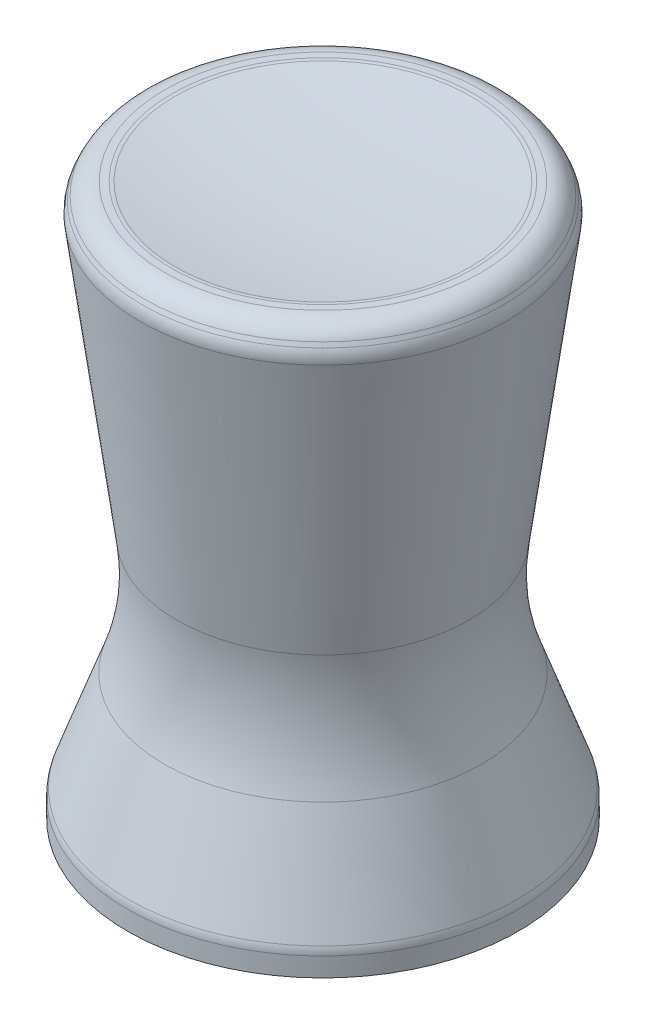
SolidWorks part; units mm, degrees
ref_plane "Front Plane" through (0, 0, 0) normal (0, 0, 1) x (1, 0, 0)
ref_plane "Top Plane" through (0, 0, 0) normal (0, 1, 0) x (1, 0, 0)
ref_plane "Right Plane" through (0, 0, 0) normal (1, 0, 0) x (0, 0, -1)
sketch "Sketch1" plane through (0, 0, 0) normal (0, 0, 1) x (1, 0, 0)
  line L0 (0, 0) -> (8.5, 0)
  line L1 (8.5, 0) -> (8.5, 1)
  line L2 (8.5, 1) -> (6, 8)
  line L3 (6, 8) -> (8, 23)
  line L4 (8, 23) -> (7.5, 24)
  line L5 (7.5, 24) -> (6.5, 24)
  line L6 (6.5, 24) -> (3.2692, 23.5) construction
  line L7 (0, 23.5) -> (0, 0) construction
  line L8 (0, 0) -> (0, 23.5)
  line L9 (3.2692, 23.5) -> (0, 23.5) construction
  spline S0 degree 2 poles (6.5, 24) (3.2692, 23.5) (0, 23.5) knots 0 0 0 1 1 1
  dimension "D1" = 24
  dimension "D2" = 8
  dimension "D3" = 1
  dimension "D4" = 8
  dimension "D5" = 1
  dimension "D6" = 0.5
  dimension "D7" = 0.5
  dimension "D8" = 1
  dimension "D9" = 8.5
  dimension "D10" = 6
revolve "Revolve1" add sketch "Sketch1" angle 360 about L7
fillet "Fillet1" radius 11 1 edges at (-6, 8, 0)
fillet "Fillet2" radius 1 4 edges at (-6.5, 24, 0) (-7.5, 24, 0) (-8, 23, 0) (-8.5, 1, 0)
sketch "Sketch3" plane through (0, 0, 0) normal (0, 0, 1) x (1, 0, 0)
  line L0 (0, 0) -> (3.875, 0)
  line L1 (-8.5, 0) -> (8.5, 0) construction
  line L2 (3.875, 0) -> (3.875, 6.5)
  line L3 (3.875, 6.5) -> (3.05, 7.325)
  line L4 (3.05, 7.325) -> (3.05, 17.75)
  line L5 (3.05, 17.75) -> (0, 17.75)
  line L6 (0, 17.75) -> (0, 0)
  dimension "D1" = 17.75
  dimension "D2" = 3.875
  dimension "D3" = 45
  dimension "D4" = 3.05
  dimension "D5" = 6.5
revolve "Cut-Revolve1" cut sketch "Sketch3" angle 360 about L6
ref_plane "Plane1" through (0, 7.325, 0) normal (0, 1, 0) x (1, 0, 0)
sketch "Sketch4" plane through (0, 17.75, 0) normal (0, -1, 0) x (1, 0, 0)
  line L0 (-999.9068, -3) -> (49000.0932, -3) construction
  line L1 (-2.6557, 4.6) -> (2.6557, 4.6)
  line L2 (-2.6557, 4.6) -> (-2.6557, 1.5)
  line L3 (-2.6557, 1.5) -> (2.6557, 1.5)
  line L4 (2.6557, 4.6) -> (2.6557, 1.5)
  line L5 (-2.6557, 4.6) -> (2.6557, 1.5) construction
  line L6 (-2.6557, 1.5) -> (2.6557, 4.6) construction
  line L7 (55, 0) -> (-55, 0) construction
  circle A0 centre (0, 0) radius 3.05 construction
  circle A1 centre (0, 0) radius 3.05 construction
  circle A2 centre (0, -3.05) radius 0.1
  point P0 (0, 3.05)
  dimension "D1" = 3
  dimension "D3" = 0.2
  dimension "D2" = 4.5
extrude "Boss-Extrude1" add sketch "Sketch4" along normal up to surface (10.425 mm away) up to plane "Plane1"
chamfer "Chamfer1" distance 0.35 angle 45 1 edges at (0, 7.325, 1.5)
